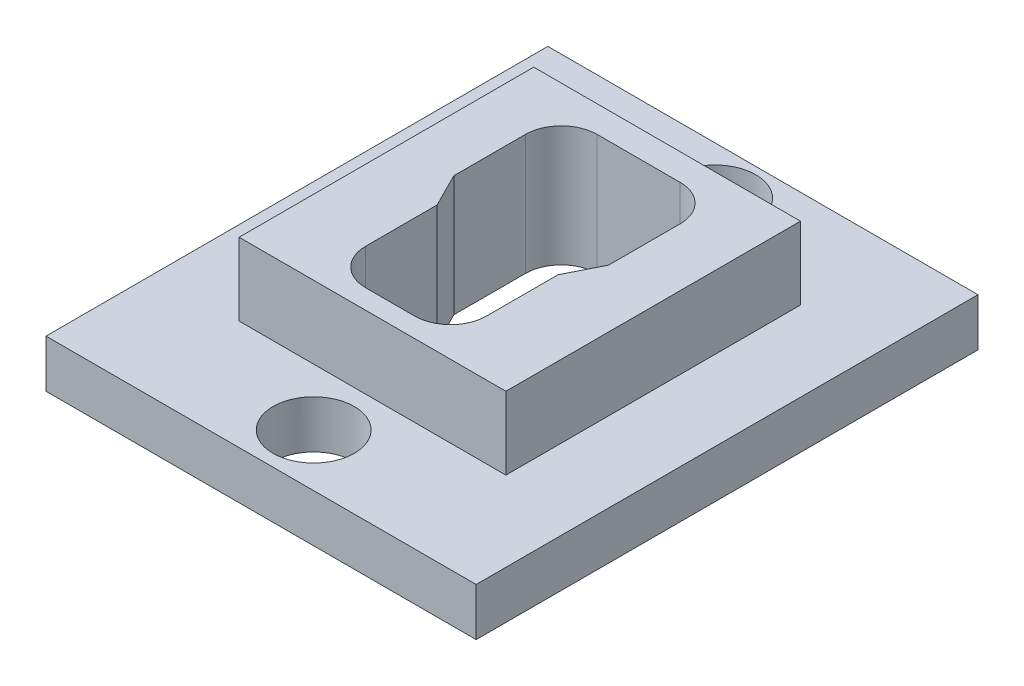
SolidWorks part; units mm, degrees
ref_plane "Front Plane" through (0, 0, 0) normal (0, 0, 1) x (1, 0, 0)
ref_plane "Top Plane" through (0, 0, 0) normal (0, 1, 0) x (1, 0, 0)
ref_plane "Right Plane" through (0, 0, 0) normal (1, 0, 0) x (0, 0, -1)
sketch "Sketch1" plane through (0, 0, 0) normal (0, 1, 0) x (1, 0, 0)
  line L0 (0, 0) -> (0, 13.208) construction
  line L1 (2.2087, 6.604) -> (-2.2087, 6.604)
  line L2 (0, 0) -> (13.208, 0) construction
  line L3 (-4.1137, 4.699) -> (-4.1137, 0.8928)
  line L4 (0, 0) -> (0, -13.208) construction
  line L5 (0, -6.604) -> (-1.3081, -6.604)
  line L6 (-3.2131, -4.699) -> (-3.2131, -0.8928)
  line L7 (-4.1137, 0.8928) -> (-3.2131, -0.8928)
  line L8 (4.1137, 0.8928) -> (3.2131, -0.8928)
  line L9 (4.1137, 4.699) -> (4.1137, 0.8928)
  line L10 (3.2131, -4.699) -> (3.2131, -0.8928)
  line L11 (0, -6.604) -> (1.3081, -6.604)
  line L12 (-11.43, 13.208) -> (11.43, 13.208)
  line L13 (11.43, 13.208) -> (11.43, -13.462)
  line L14 (11.43, -13.462) -> (-11.43, -13.462)
  line L15 (-11.43, 13.208) -> (-11.43, -13.462)
  arc A1 (-2.2087, 6.604) -> (-4.1137, 4.699) centre (-2.2087, 4.699) ccw
  arc A2 (-1.3081, -6.604) -> (-3.2131, -4.699) centre (-1.3081, -4.699) cw
  arc A3 (2.2087, 6.604) -> (4.1137, 4.699) centre (2.2087, 4.699) cw
  arc A4 (1.3081, -6.604) -> (3.2131, -4.699) centre (1.3081, -4.699) ccw
  point P17 (0, 6.604)
  point P27 (0, -13.462)
  dimension "D3" = 1.905
  dimension "D4" = 1.905
  dimension "D5" = 11.43
  dimension "D1" = 6.604
  dimension "D2" = 6.604
  dimension "D6" = 26.67
extrude "Boss-Extrude2" add sketch "Sketch1" along normal blind 6.4008
sketch "Sketch4" plane through (0, 6.4008, 0) normal (0, 1, 0) x (1, 0, 0)
  line L0 (0, 0) -> (11.43, 0) construction
  line L1 (11.43, -13.462) -> (11.43, 13.208) construction
  circle A0 centre (0, 10.668) radius 2.159
  circle A1 centre (0, -10.668) radius 2.159
  point P2 (0, -10.668)
  dimension "D1" = 10.668
sketch "Sketch5" plane through (0, 6.4008, 0) normal (0, 1, 0) x (1, 0, 0)
  line L1 (-6.9876, 8.0144) -> (7.1889, 8.0144)
  line L2 (-6.9876, 8.0144) -> (-6.9876, -7.6405)
  line L3 (-6.9876, -7.6405) -> (7.1889, -7.6405)
  line L4 (7.1889, 8.0144) -> (7.1889, -7.6405)
  line L5 (-11.43, 13.208) -> (11.43, 13.208)
  line L6 (-11.43, 13.208) -> (-11.43, -13.462)
  line L7 (-11.43, -13.462) -> (11.43, -13.462)
  line L8 (11.43, 13.208) -> (11.43, -13.462)
extrude "Cut-Extrude2" cut sketch "Sketch4" against normal through all both and the other way through all
extrude "Cut-Extrude3" cut sketch "Sketch5" against normal blind 3.8608
